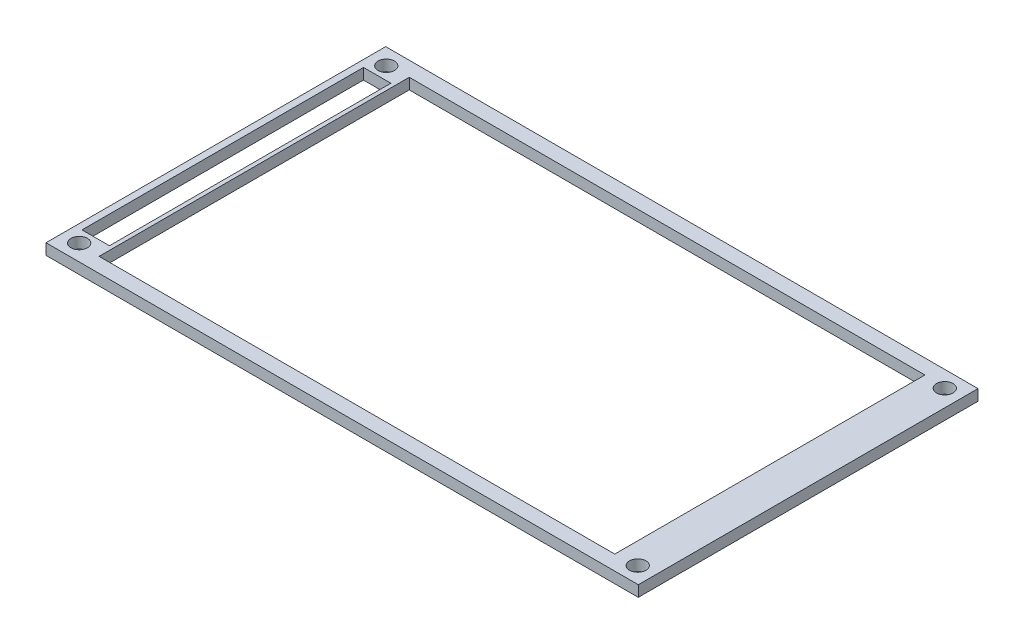
SolidWorks part; units mm, degrees
ref_plane "Front Plane" through (0, 0, 0) normal (0, 0, 1) x (1, 0, 0)
ref_plane "Top Plane" through (0, 0, 0) normal (0, 1, 0) x (1, 0, 0)
ref_plane "Right Plane" through (0, 0, 0) normal (1, 0, 0) x (0, 0, -1)
sketch "Sketch1" plane through (0, 0, 0) normal (0, 1, 0) x (1, 0, 0)
  line L1 (-54, 30.9684) -> (54, 30.9684)
  line L2 (-54, 30.9684) -> (-54, -30.9684)
  line L3 (-54, -30.9684) -> (54, -30.9684)
  line L4 (54, 30.9684) -> (54, -30.9684)
  line L5 (-54, 30.9684) -> (54, -30.9684) construction
  line L6 (-54, -30.9684) -> (54, 30.9684) construction
  point P0 (0, 0)
  dimension "D1" = 108
extrude "Boss-Extrude1" add sketch "Sketch1" along normal blind 2
sketch "Sketch2" plane through (0, 2, 0) normal (0, 1, 0) x (1, 0, 0)
  line L0 (-54, 30.9684) -> (-50.9216, 27.9966)
  line L1 (-54, 30.9684) -> (-54, -30.9684) construction
  line L3 (-54, 0) -> (54, 0) construction
  line L4 (54, -30.9684) -> (54, 30.9684) construction
  line L5 (0, 30.9684) -> (0, -30.9684) construction
  line L6 (54, 30.9684) -> (-54, 30.9684) construction
  line L7 (-54, -30.9684) -> (54, -30.9684) construction
  circle A0 centre (-50.9216, 27.9966) radius 1.5
  point P17 (-50.9216, 27.3306)
ref_plane "Plane1" through (0, 0, 0) normal (0, 0, 1) x (1, 0, 0)
ref_plane "Plane2" through (0, 0, 0) normal (-1, 0, 0) x (0, 0, 1)
extrude "Cut-Extrude1" cut sketch "Sketch2" against normal through all contours A0
mirror "Mirror1" about plane through (0, 0, 0) normal (0, 0, 1) of "Cut-Extrude1"
mirror "Mirror2" about plane through (0, 0, 0) normal (-1, 0, 0) of "Mirror1"
sketch "Sketch3" plane through (0, 2, 0) normal (0, 1, 0) x (1, 0, 0)
  line L1 (-47.0124, -28.2777) -> (47.0124, -28.2777)
  line L2 (-47.0124, -28.2777) -> (-47.0124, 28.2777)
  line L3 (-47.0124, 28.2777) -> (47.0124, 28.2777)
  line L4 (47.0124, -28.2777) -> (47.0124, 28.2777)
  line L5 (-47.0124, -28.2777) -> (47.0124, 28.2777) construction
  line L6 (-47.0124, 28.2777) -> (47.0124, -28.2777) construction
  point P0 (0, 0)
extrude "Cut-Extrude2" cut sketch "Sketch3" against normal through all
sketch "Sketch4" plane through (0, 2, 0) normal (0, 1, 0) x (1, 0, 0)
  line L0 (-34.0652, 0) -> (34.0652, 0) construction
  line L1 (-47.7447, -25.6583) -> (-52.7454, -25.6583)
  line L2 (-47.7447, -25.6583) -> (-47.7447, 25.6583)
  line L3 (-47.7447, 25.6583) -> (-52.7454, 25.6583)
  line L4 (-52.7454, -25.6583) -> (-52.7454, 25.6583)
  line L5 (-47.7447, -25.6583) -> (-52.7454, 25.6583) construction
  line L6 (-47.7447, 25.6583) -> (-52.7454, -25.6583) construction
  point P0 (-50.2451, 0)
extrude "Cut-Extrude3" cut sketch "Sketch4" against normal through all
